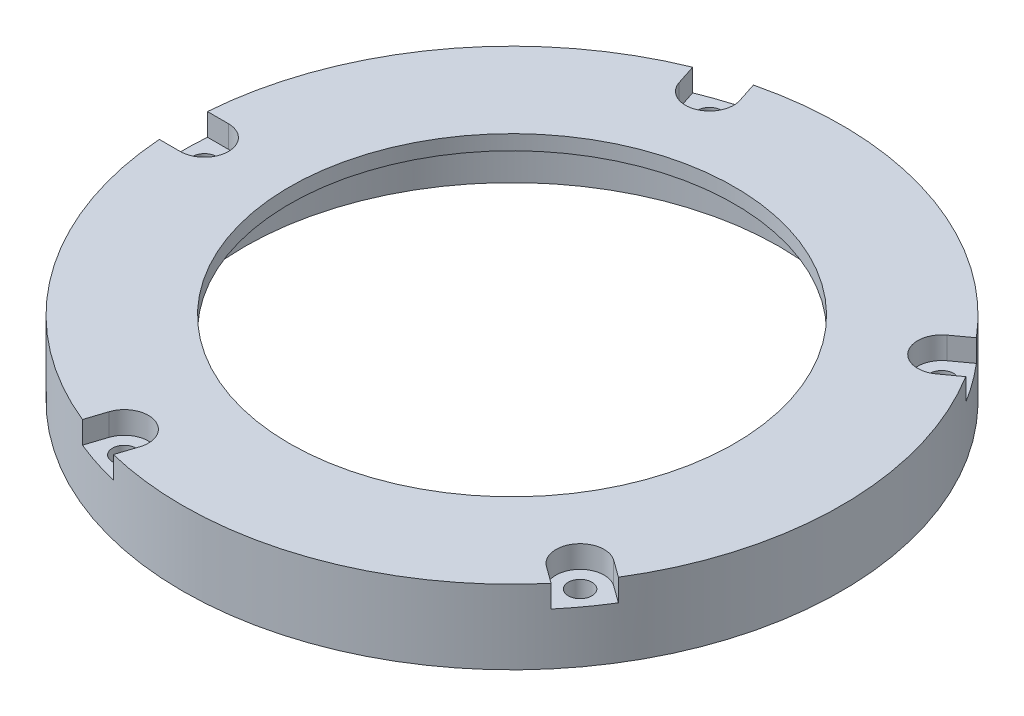
SolidWorks part; units mm, degrees
ref_plane "Front Plane" through (0, 0, 0) normal (0, 0, 1) x (1, 0, 0)
ref_plane "Top Plane" through (0, 0, 0) normal (0, 1, 0) x (1, 0, 0)
ref_plane "Right Plane" through (0, 0, 0) normal (1, 0, 0) x (0, 0, -1)
sketch "Sketch1" plane through (0, 0, 0) normal (0, 1, 0) x (1, 0, 0)
  circle A0 centre (0, 0) radius 44.45
  circle A1 centre (0, 0) radius 36.05
  circle A2 centre (0, 0) radius 30
  dimension "D1" = 60
  dimension "D2" = 72.1
  dimension "D3" = 88.9
extrude "Boss-Extrude1" add sketch "Sketch1" against normal blind 2 contours A1 A2 | A0 A1 region at (-43.1928, 0, 0) region at (-35.0304, 0, 0)
extrude "Boss-Extrude2" add sketch "Sketch1<3>" against normal blind 8 from surface contours A0 A1 region at (-43.1928, 0, 0) starting at face at (0, -2, 30)
sketch "Sketch1<3>" plane through (0, 0, 0) normal (0, 1, 0) x (1, 0, 0) same geometry as "Sketch1"
hole_wizard "CBORE for M3 SHCS2" positions "Sketch6" profile "Sketch7" counterbore size "M3" standard "ANSI Metric" end condition through all
sketch "Sketch6" plane through (0, 0, 0) normal (0, 1, 0) x (1, 0, 0)
  line L0 (0, 0) -> (-41.5, 0) construction
  point P2 (-41.5, 0)
  dimension "D1" = 41.5
sketch "Sketch7" plane through (-41.5, 0, 0) normal (1, 0, 0) x (0, 0, 1)
  line L0 (0, 0) -> (0, 10)
  line L1 (0, 10) -> (1.6, 10)
  line L3 (1.6, 10) -> (1.6, 3)
  line L4 (1.6, 3) -> (3.25, 3)
  line L5 (3.25, 3) -> (3.25, 0)
  line L7 (3.25, 0) -> (0, 0)
  line L11 (0, -6.35) -> (0, 107.95) construction
  dimension "Thru Hole Dia." = 3.2
  dimension "Thru Hole Depth" = 10
  dimension "C'Bore Dia." = 6.5
  dimension "C'Bore Depth" = 3
sketch "Sketch8" plane through (0, -3, 0) normal (0, 1, 0) x (1, 0, 0)
  line L1 (-41.5, 3.25) -> (-44.45, 3.25)
  line L2 (-41.5, 3.25) -> (-41.5, -3.25)
  line L3 (-41.5, -3.25) -> (-44.45, -3.25)
  line L4 (-44.45, 3.25) -> (-44.45, -3.25)
  arc A2 (-44.4276, 1.4113) -> (-44.4276, -1.4113) centre (0, 0) ccw
  arc A3 (-44.4276, -1.4113) -> (-44.4276, 1.4113) centre (-41.5, 0) ccw
  arc A4 (-44.4276, 1.4113) -> (-44.4276, -1.4113) centre (0, 0) ccw
  arc A5 (-44.4276, -1.4113) -> (-44.4276, 1.4113) centre (-41.5, 0) ccw
  arc M4 (-44.4276, 1.4113) -> (-44.4276, -1.4113) centre (0, 0) ccw
  arc M5 (-44.4276, -1.4113) -> (-44.4276, 1.4113) centre (-41.5, 0) ccw
  circle M6 centre (-41.5, 0) radius 1.6
  dimension "D1" = 0
extrude "Cut-Extrude1" cut sketch "Sketch8" along normal through all contours L2 M5 M4 M6 | L1 L4 M4 M5 | L4 L3 M4 M5 region at (-43.7661, -3, -2.7196) region at (-41.5714, -3, -2.425) region at (-43.7661, -3, 2.7196)
pattern_circular "CirPattern1" count 5 over 360 about axis through (0, -2, 0) along (0, 1, 0) of "Cut-Extrude1", "CBORE for M3 SHCS2" reverse direction yes
equation "\"Ratio\"= 15"
equation "\"Hull Diameter\"= 3.5in"
equation "\"Fixed Ring Diameter\"= 76"
equation "\"Fixed Pin Diameter\"= 6"
equation "\"Output Ring Diameter\"= 40"
equation "\"Output Pin Diameter\"= 6"
equation "\"Disk Bearing Inner Diameter\"= 9"
equation "\"Disk Bearing Outer Diameter\"= 17"
equation "\"Disk Bearing Height\"= 5"
equation "\"Shaft Bearing Inner Diameter\"= 15"
equation "\"Shaft Bearing Outer Diameter\"= 21"
equation "\"Shaft Bearing Height\"= 4"
equation "\"Eccentricity\"= 1.5"
equation "\"Disk Height\"= 8"
equation "\"Disk Spacing\"= 5"
equation "\"Hull Height\"= 40"
equation "\"Shaft End Bearing Inner Diameter\"= 12"
equation "\"Shaft End Bearing Outer Diameter\"= 18"
equation "\"Shaft End Bearing Height\"= 4"
equation "\"Output Bearing Inner Diameter\"= 55"
equation "\"Output Bearing Outer Diameter\"= 72"
equation "\"Outer Bearing Height\"= 9"
equation "\"D1@Sketch1\"=\"Output Bearing Inner Diameter\"+5"
equation "\"D2@Sketch1\"=\"Output Bearing Outer Diameter\"+0.1"
equation "\"D3@Sketch1\"=\"Hull Diameter\""
